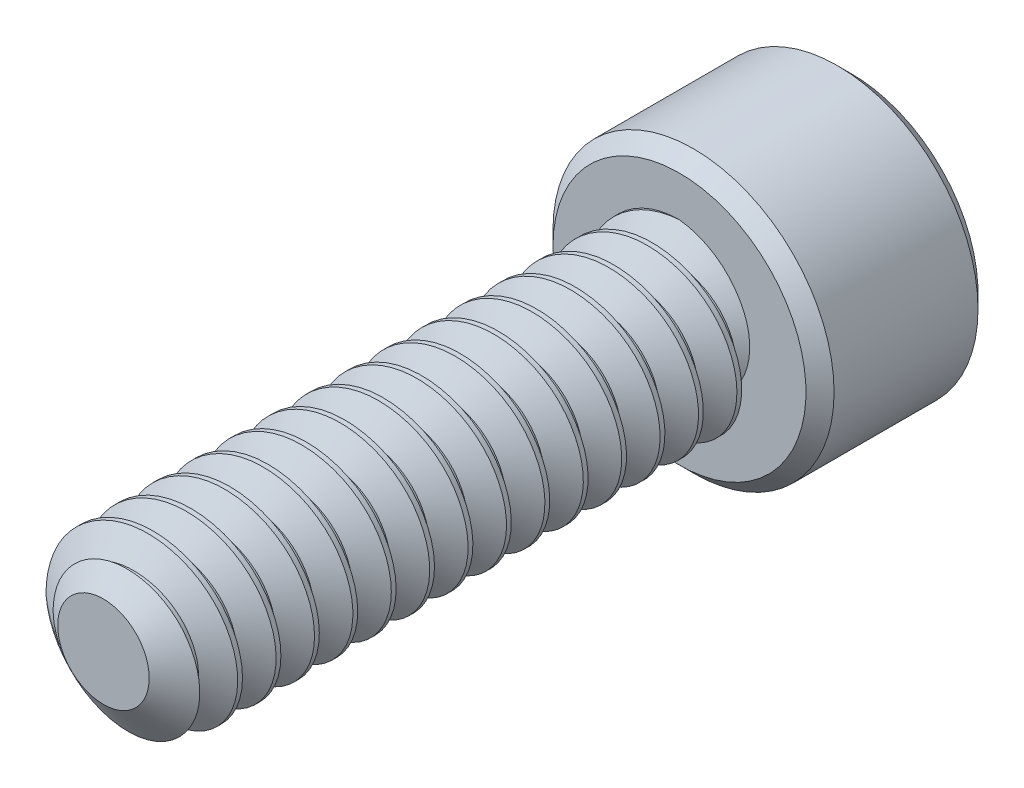
SolidWorks part; units mm, degrees
ref_plane "Front Plane" through (0, 0, 0) normal (0, 0, 1) x (1, 0, 0)
ref_plane "Top Plane" through (0, 0, 0) normal (0, 1, 0) x (1, 0, 0)
ref_plane "Right Plane" through (0, 0, 0) normal (1, 0, 0) x (0, 0, -1)
sketch "Sketch1" plane through (0, 0, 0) normal (0, 0, 1) x (1, 0, 0)
  circle A0 centre (0, 0) radius 1.4224
  dimension "OD" = 2.8448
extrude "Extrude1" add sketch "Sketch1" against normal blind 9.525
sketch "Sketch2" plane through (0, 0, 0) normal (0, 0, 1) x (1, 0, 0)
  circle A0 centre (0, 0) radius 1.4224 construction
  circle A1 centre (0, 0) radius 1.4224
curve "Helix/Spiral1" pitch 0.635 height 10.16 radius 1.4224 centre (0, 0, 0) axis (0, 0, -1) start towards (0, 1, 0) parameters "pitch"=0.635
sketch "Sketch3" plane through (0, 0, 0) normal (1, 0, 0) x (0, 0, -1)
  line L0 (-0.5556, 1.4224) -> (-0.3175, 1.01)
  line L1 (-0.3175, 1.01) -> (-0.2381, 1.01)
  line L2 (-0.2381, 1.01) -> (0, 1.4224)
  line L3 (-0.5556, 1.4224) -> (0, 1.4224)
  line L4 (-0.2778, 1.4224) -> (-0.2778, 1.01) construction
  line L5 (-0.4366, 1.2162) -> (-0.1191, 1.2162) construction
  line L6 (0, 1.4224) -> (0, -1.4224) construction
  dimension "D1" = 0.0794
  dimension "D2" = 0.3175
  dimension "D3" = 60
sweep "Cut-Sweep1" cut profiles "Sketch3" path "Helix/Spiral1"
sketch "Sketch4" plane through (0, 0, 0) normal (1, 0, 0) x (0, 0, -1)
  line L0 (0.4666, 1.4224) -> (0, 0.756)
  line L1 (0, 0.756) -> (0, 1.4224)
  line L2 (0.4666, 1.4224) -> (0, 1.4224)
  line L3 (-0.5556, 1.4224) -> (0, 1.4224) construction
  line L4 (0, 0) -> (7.0209, 0) construction
  dimension "D1" = 55
  dimension "D2" = 0.254
revolve "Cut-Revolve1" cut sketch "Sketch4" angle 360 about L4
sketch "Sketch5" plane through (0, 0, 0) normal (1, 0, 0) x (0, 0, -1)
  line L0 (9.525, -1.0232) -> (9.525, 1.0149) construction
  line L1 (9.525, 1.5494) -> (87.4327, 1.5494)
  line L2 (9.525, 1.5494) -> (9.525, 0)
  line L3 (9.525, 0) -> (87.3125, 0)
  line L4 (87.3125, 1.2192) -> (87.3125, 0)
  line L5 (87.4327, 1.5494) -> (87.3125, 1.2192)
  line L6 (0, 0) -> (9.9695, 0) construction
  point P3 (87.3125, 1.5494)
  point P10 (87.3125, 1.5494)
  dimension "D1" = 0.3302
  dimension "Thread min" = 87.3125
  dimension "D2" = 0.127
  dimension "D3" = 20
revolve "partially thread" [suppressed] add sketch "Sketch5" angle 360 about L6
sketch "Sketch6" plane through (0, 0, -9.525) normal (0, 0, -1) x (-1, 0, 0)
  circle A0 centre (0, 0) radius 2.3241
  dimension "head dia" = 4.6482
extrude "Extrude2" add sketch "Sketch6" along normal blind 2.8448
sketch "Sketch7" plane through (0, 0, -12.3698) normal (0, 0, -1) x (-1, 0, 0)
  line L1 (0, 1.3748) -> (-1.1906, 0.6874)
  line L2 (-1.1906, 0.6874) -> (-1.1906, -0.6874)
  line L3 (-1.1906, -0.6874) -> (0, -1.3748)
  line L4 (0, -1.3748) -> (1.1906, -0.6874)
  line L5 (1.1906, -0.6874) -> (1.1906, 0.6874)
  line L6 (1.1906, 0.6874) -> (0, 1.3748)
  circle A0 centre (0, 0) radius 1.1906 construction
  dimension "hex dia" = 2.3813
extrude "Cut-Extrude1" cut sketch "Sketch7" against normal blind 1.7859
sketch "Sketch8" plane through (0, 0, -12.3698) normal (0, 0, -1) x (-1, 0, 0)
  circle A0 centre (0, 0) radius 1.3748
extrude "Cut-Extrude2" cut sketch "Sketch8" against normal through all draft 45
chamfer "Chamfer1" distance 0.2324 angle 45 2 edges at (-2.3241, 0, -12.3698) (-2.3241, 0, -9.525)
sketch "Sketch9" plane through (0, 0, 0) normal (1, 0, 0) x (0, 0, -1)
  line L0 (0, 1.4224) -> (0, -1.4224) construction
  line L1 (3.4925, 1.4224) -> (3.4925, -1.4224) construction
  dimension "D1" = 3.4925
equation "\"D3@Helix/Spiral1\" = \"screw length@Extrude1\"+\"pitch@Helix/Spiral1\""
equation "\"D1@Sketch3\" = \"pitch@Helix/Spiral1\"*.125"
equation "\"D2@Sketch3\" = \"pitch@Helix/Spiral1\"*.5"
equation "\"D1@Cut-Extrude1\" = \"hex dia@Sketch7\"*.75"
equation "\"D1@Chamfer1\" = \"head dia@Sketch6\"*.05"
equation "\"D1@Sketch9\" = \"pitch@Helix/Spiral1\"*5.5"
